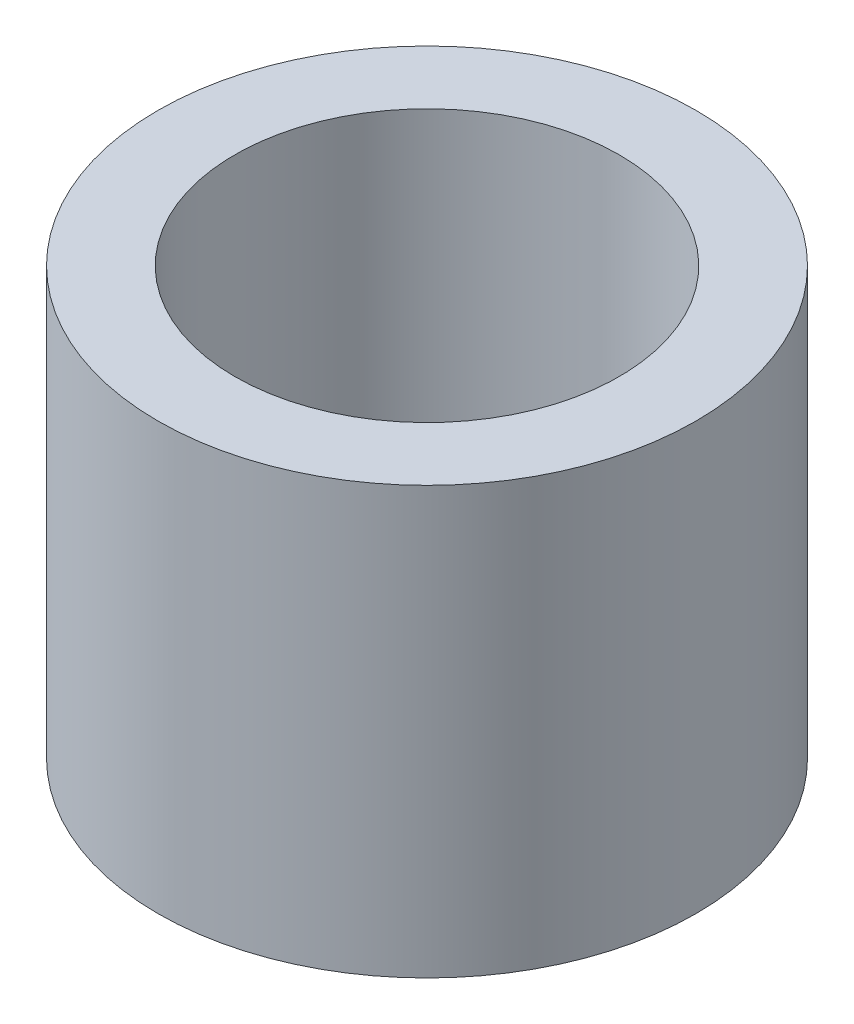
SolidWorks part; units mm, degrees
material "Fireplace Stuff"
ref_plane "Front Plane" through (0, 0, 0) normal (0, 0, 1) x (1, 0, 0)
ref_plane "Top Plane" through (0, 0, 0) normal (0, 1, 0) x (1, 0, 0)
ref_plane "Right Plane" through (0, 0, 0) normal (1, 0, 0) x (0, 0, -1)
sketch "Sketch3" plane through (0, 0, 0) normal (0, 1, 0) x (1, 0, 0)
  circle A0 centre (0, 0) radius 44.45
  circle A2 centre (0, 0) radius 31.75
  dimension "D1" = 88.9
  dimension "D2" = 12.7
extrude "Boss-Extrude1" add sketch "Sketch3" along normal blind 70.485
